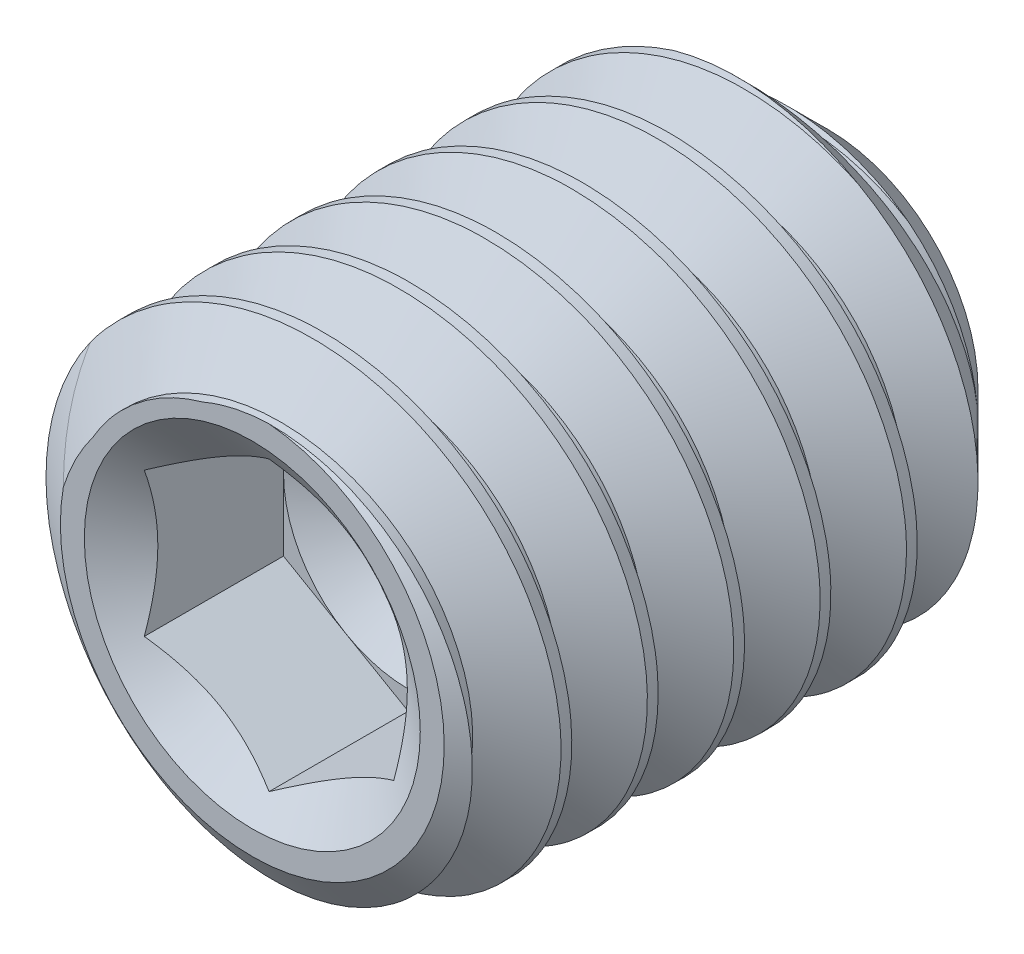
SolidWorks part; units mm, degrees
ref_plane "Front Plane" through (0, 0, 0) normal (0, 0, 1) x (1, 0, 0)
ref_plane "Top Plane" through (0, 0, 0) normal (0, 1, 0) x (1, 0, 0)
ref_plane "Right Plane" through (0, 0, 0) normal (1, 0, 0) x (0, 0, -1)
sketch "Sketch1" plane through (0, 0, 0) normal (1, 0, 0) x (0, 0, -1)
  line L0 (-1.3174, 0) -> (-1.3174, 1)
  line L1 (-1.3174, 1) -> (-1.1423, 1.25)
  line L2 (-1.1423, 1.25) -> (1.2139, 1.25)
  line L3 (1.2139, 1.25) -> (1.6826, 0.7813)
  line L5 (1.3174, 0) -> (-1.3174, 0)
  line L6 (1.3174, 0) -> (1.6826, 0) construction
  line L7 (1.6826, 0) -> (1.6826, 0.7813) construction
  line L8 (1.6826, -0.7813) -> (1.3174, 0) construction
  line L9 (-1.1423, -1.25) -> (1.2139, -1.25) construction
  line L10 (0, 0) -> (0, -0.45) construction
  line L11 (1.3174, 0) -> (1.5934, 0.4594)
  line L12 (1.3174, 0) -> (1.5934, -0.4594) construction
  arc A0 (1.5934, 0.4594) -> (1.6826, 0.7813) centre (1.0576, 0.7813) ccw
  arc A1 (1.5934, -0.4594) -> (1.6826, -0.7813) centre (1.0576, -0.7813) cw construction
  point P11 (-1.3174, 1.25)
  point P12 (0.1076, -1.25)
  point P13 (-0.1924, -1.25)
  point P14 (1.6826, 1.25)
  dimension "D5" = 0.625
  dimension "Thread Size" = 2.5
  dimension "Length" = 3
  dimension "D3" = 35
  dimension "D6" = 45
  dimension "D7" = 2
  dimension "Thread Pitch" = 0.45
  dimension "D2" = 1.125
  dimension "D4" = 59
  dimension "D8" = 1.5625
  dimension "D1" = 1.575
sketch "Sketch2" plane through (0, 0, 0) normal (0, 0, 1) x (1, 0, 0)
  line L1 (0.65, 0.3753) -> (0, 0.7506) construction
  line L2 (0, 0.7506) -> (-0.65, 0.3753) construction
  line L3 (-0.65, 0.3753) -> (-0.65, -0.3753) construction
  line L4 (-0.65, -0.3753) -> (0, -0.7506) construction
  line L5 (0, -0.7506) -> (0.65, -0.3753) construction
  line L6 (0.65, -0.3753) -> (0.65, 0.3753) construction
  circle A0 centre (0, 0) radius 0.65 construction
  circle A1 centre (0, 0) radius 1.25 construction
  dimension "Drive Size" = 1.3
sketch "Sketch4" plane through (0, 0, 0) normal (1, 0, 0) x (0, 0, -1)
  line L0 (1.3174, 0) -> (1.5934, 0.4594) construction
  line L1 (-1.1423, 1.25) -> (1.2139, 1.25) construction
  line L2 (-1.3174, 0) -> (-1.3174, 1) construction
  line L3 (1.3174, 0) -> (-1.3174, 0) construction
  line L4 (1.3174, 0) -> (1.5934, 0.4594)
  line L5 (1.2139, 1.25) -> (1.6826, 0.7813) construction
  line L6 (1.2139, 1.25) -> (1.6826, 0.7813)
  line L8 (1.3174, 0) -> (-1.3174, 0)
  line L9 (-1.3174, 0) -> (-1.3174, 1)
  line L10 (-1.1423, 1.25) -> (1.2139, 1.25)
  line L11 (-1.3174, 1) -> (-1.1423, 1.25) construction
  line L12 (-1.3174, 1) -> (-1.1423, 1.25)
  arc A0 (1.5934, 0.4594) -> (1.6826, 0.7813) centre (1.0576, 0.7813) ccw construction
  arc A1 (1.5934, 0.4594) -> (1.6826, 0.7813) centre (1.0576, 0.7813) ccw
revolve "Revolve1" add sketch "Sketch4" angle 360 about L8
sketch "Sketch6" plane through (0, 0, 1.3174) normal (0, 0, 1) x (1, 0, 0)
  line L1 (0.65, 0.3753) -> (0, 0.7506)
  line L2 (0, 0.7506) -> (-0.65, 0.3753)
  line L3 (-0.65, 0.3753) -> (-0.65, -0.3753)
  line L4 (-0.65, -0.3753) -> (0, -0.7506)
  line L5 (0, -0.7506) -> (0.65, -0.3753)
  line L6 (0.65, -0.3753) -> (0.65, 0.3753)
  circle A0 centre (0, 0) radius 0.65 construction
  dimension "D1" = 1.3
extrude "Cut-Extrude3" cut sketch "Sketch6" against normal blind 0.8125
sketch "Sketch7" plane through (0, 0, 1.3174) normal (0, 0, 1) x (1, 0, 0)
  line L0 (0, 0.7506) -> (0, 1) construction
  circle A0 centre (0, 0) radius 0.8753
  circle A2 centre (0, 0) radius 1 construction
  point P6 (0, 0.8753)
  point P10 (0, 0.8753)
extrude "Cut-Extrude4" cut sketch "Sketch7" against normal through all draft 55
sketch "Sketch8" plane through (0, 0, 0.5049) normal (0, 0, 1) x (1, 0, 0)
  circle A0 centre (0, 0) radius 0.65 construction
  circle A1 centre (0, 0) radius 0.65
extrude "Cut-Extrude5" cut sketch "Sketch8" against normal through all draft 60
ref_plane "Plane1" through (0, 0, -1.6826) normal (0, 0, 1) x (1, 0, 0)
sketch "Sketch9" plane through (0, 0, -1.6826) normal (0, 0, 1) x (1, 0, 0)
  circle A0 centre (0, 0) radius 1.25 construction
  circle A1 centre (0, 0) radius 1.25
curve "Helix/Spiral1" pitch 0.45 height 3.45 radius 1.25 centre (0, 0, -1.6826) axis (0, 0, 1) start towards (0, 1, 0)
sketch "Sketch10" plane through (0, 0, 0) normal (1, 0, 0) x (0, 0, -1)
  line L0 (1.6826, 1.25) -> (2.0764, 1.25)
  line L1 (2.0764, 1.25) -> (1.9076, 0.9577)
  line L2 (1.8514, 0.9577) -> (1.6826, 1.25)
  line L3 (1.8514, 0.9577) -> (1.9076, 0.9577)
  line L4 (1.8795, 0.9577) -> (1.8795, 1.25) construction
  line L5 (1.767, 1.1039) -> (1.992, 1.1039) construction
  point P10 (1.8795, 1.1039)
  dimension "D1" = 60
  dimension "D2" = 0.0563
  dimension "D3" = 0.225
sweep "Cut-Sweep1" cut profiles "Sketch10" path "Helix/Spiral1"
equation "\"D7@Sketch1\" = \"Thread Size@Sketch1\" * .8"
equation "\"D3\"= \"Length@Sketch1\" + \"Thread Pitch@Sketch1\""
equation "\"D4\"= \"Thread Pitch@Sketch1\""
equation "\"D1@Sketch6\"=\"Drive Size@Sketch2\""
equation "\"D1@Cut-Extrude3\"=\"Drive Size@Sketch2\"*.625"
equation "\"D3@Helix/Spiral1\"=\"Length@Sketch1\"+\"Thread Pitch@Sketch1\""
equation "\"D4@Helix/Spiral1\"=\"Thread Pitch@Sketch1\""
equation "\"D2@Sketch10\"=\"Thread Pitch@Sketch1\"/8"
equation "\"D3@Sketch10\"=\"Thread Pitch@Sketch1\"/2"
equation "\"D2@Sketch1\"=\"Thread Pitch@Sketch1\"*2.5"
equation "\"D5@Sketch1\"=\"Thread Size@Sketch1\"*.25"
equation "\"D8@Sketch1\"=\"Thread Size@Sketch1\"*.625"
equation "\"D1@Sketch1\"=\"Thread Pitch@Sketch1\"*3.5"
